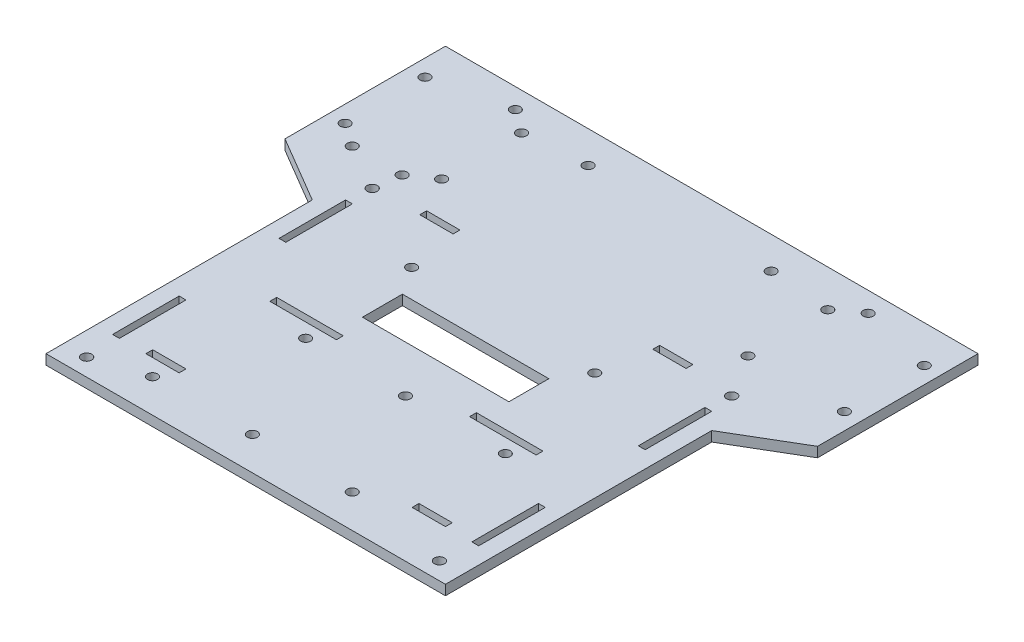
SolidWorks part; units mm, degrees
ref_plane "Front Plane" through (0, 0, 0) normal (0, 0, 1) x (1, 0, 0)
ref_plane "Top Plane" through (0, 0, 0) normal (0, 1, 0) x (1, 0, 0)
ref_plane "Right Plane" through (0, 0, 0) normal (1, 0, 0) x (0, 0, -1)
sketch "Sketch1" plane through (0, 0, 0) normal (0, 1, 0) x (1, 0, 0)
  line L0 (-60, 10) -> (-80, 21.7918)
  line L1 (60, -70) -> (-60, -70)
  line L2 (60, -70) -> (60, 70)
  line L3 (60, 70) -> (-60, 70)
  line L4 (-60, -70) -> (-60, 70)
  line L5 (60, -70) -> (-60, 70) construction
  line L6 (60, 70) -> (-60, -70) construction
  line L7 (-80, 21.7918) -> (-80, 70)
  line L8 (-80, 70) -> (-60, 70)
  line L9 (0, 0) -> (0, 70) construction
  line L10 (60, 10) -> (80, 21.7918)
  line L11 (80, 70) -> (60, 70)
  line L12 (80, 21.7918) -> (80, 70)
  point P0 (0, 0)
  dimension "D1" = 140
  dimension "D2" = 120
  dimension "D3" = 20
  dimension "D4" = 30.523
  dimension "D5" = 60
extrude "Boss-Extrude1" add sketch "Sketch1" along normal blind 3 contours L4 L1 L2 L3 | L8 L7 L0 L4 | L10 L12 L11 L2 region at (0, 0, 0) region at (-69.6368, 0, -42.8409) region at (69.6368, 0, -42.8409)
sketch "Sketch2" plane through (0, 3, 0) normal (0, 1, 0) x (1, 0, 0)
  line L2 (0, 0) -> (0, -70) construction
  line L3 (60, -70) -> (-60, -70) construction
  circle A0 centre (-38, -60) radius 1.5
  circle A1 centre (-25, -27) radius 1.5
  circle A2 centre (5, -27) radius 1.5
  circle A3 centre (-8, -60) radius 1.5
  circle A4 centre (35, -27) radius 1.5
  circle A5 centre (22, -60) radius 1.5
  dimension "D1" = 3
  dimension "D2" = 38
  dimension "D3" = 10
  dimension "D4" = 3
  dimension "D6" = 33
  dimension "D5" = 13
  dimension "D7" = 3
extrude "Cut-Extrude1" cut sketch "Sketch2" against normal through all
sketch "Sketch3" plane through (0, 3, 0) normal (0, 1, 0) x (1, 0, 0)
  line L0 (-0.0296, 57.8856) -> (-0.0296, -0.1144) construction
  line L1 (-30.0296, 33.8856) -> (29.9704, 33.8856) construction
  line L4 (-80, 21.7918) -> (-80, 70) construction
  line L6 (-80, 21.7918) -> (-80, 70) construction
  line L7 (80, 70) -> (-80, 70) construction
  line L8 (-60, 10) -> (-60, 70) construction
  line L9 (60, 10) -> (60, 70) construction
  circle A0 centre (-27.5296, 60.3856) radius 1.5
  circle A1 centre (-27.5296, 7.3856) radius 1.5
  circle A2 centre (27.4704, 7.3856) radius 1.5
  circle A3 centre (27.4704, 60.3856) radius 1.5
  point P16 (-80, 45.8959)
  dimension "D1" = 52.4704
  dimension "D2" = 36.1144
  dimension "D3" = 3
  dimension "D4" = 79.9704
  dimension "D5" = 26.5
extrude "Cut-Extrude3" cut sketch "Sketch3<2>" against normal through all
sketch "Sketch3<2>" plane through (0, 3, 0) normal (0, 1, 0) x (1, 0, 0) same geometry as "Sketch3"
extrude "Cut-Extrude2" cut sketch "Sketch3" against normal through all rebuild error yes
sketch "Sketch4" plane through (0, 3, 0) normal (0, 1, 0) x (1, 0, 0)
  line L0 (-60.5, 58.8639) -> (-60.5, 32.8639) construction
  line L1 (-80, 21.7918) -> (-80, 70) construction
  line L2 (80, 70) -> (-80, 70) construction
  line L3 (0, 0) -> (0, 70) construction
  circle A0 centre (-75, 34.8639) radius 1.5
  circle A1 centre (-75, 58.8639) radius 1.5
  circle A2 centre (-46, 34.8639) radius 1.5
  circle A3 centre (-46, 58.8639) radius 1.5
  circle A4 centre (46, 58.8639) radius 1.5
  circle A5 centre (46, 34.8639) radius 1.5
  circle A6 centre (75, 34.8639) radius 1.5
  circle A7 centre (75, 58.8639) radius 1.5
  dimension "D1" = 3
  dimension "D2" = 3
  dimension "D5" = 5
  dimension "D6" = 11.1361
  dimension "D7" = 5
  dimension "D3" = 24
  dimension "D4" = 14.5
extrude "Cut-Extrude4" cut sketch "Sketch4" against normal through all
sketch "Sketch5" plane through (0, 3, 0) normal (0, 1, 0) x (1, 0, 0)
  line L0 (80, 70) -> (-80, 70) construction
  line L1 (-80, 21.7918) -> (-80, 70) construction
  circle A0 centre (-68, 30) radius 1.5
  circle A1 centre (-53, 30) radius 1.5
  dimension "D1" = 3
  dimension "D2" = 3
  dimension "D3" = 40
  dimension "D4" = 40
  dimension "D6" = 12
  dimension "D5" = 15
extrude "Cut-Extrude5" cut sketch "Sketch5" against normal blind 3
sketch "Sketch6" plane through (0, 3, 0) normal (0, 1, 0) x (1, 0, 0)
  line L0 (60, -70) -> (-60, -70) construction
  line L1 (-45, -52.95) -> (-35, -52.95)
  line L2 (-45, -52.95) -> (-45, -55)
  line L3 (-45, -55) -> (-35, -55)
  line L4 (-35, -52.95) -> (-35, -55)
  line L5 (-45, -52.95) -> (-35, -55) construction
  line L6 (-45, -55) -> (-35, -52.95) construction
  line L7 (-60, -70) -> (-60, 10) construction
  line L8 (0, 0) -> (0, -70) construction
  line L9 (35, -52.95) -> (35, -55)
  line L10 (45, -55) -> (35, -55)
  line L11 (45, -52.95) -> (45, -55)
  line L12 (45, -52.95) -> (35, -52.95)
  line L13 (20, -22.75) -> (20, -20.7)
  line L14 (-20, -22.75) -> (-40, -22.75)
  line L15 (-20, -22.75) -> (-20, -20.7)
  line L16 (-20, -20.7) -> (-40, -20.7)
  line L17 (-40, -22.75) -> (-40, -20.7)
  line L18 (-20, -22.75) -> (-40, -20.7) construction
  line L19 (-20, -20.7) -> (-40, -22.75) construction
  line L20 (20, -22.75) -> (40, -22.75)
  line L21 (40, -22.75) -> (40, -20.7)
  line L22 (20, -20.7) -> (40, -20.7)
  line L23 (-60, -30) -> (60, -30) construction
  line L24 (60, -70) -> (60, 10) construction
  line L25 (-30, -21.725) -> (60, -21.725) construction
  line L26 (30, 24.35) -> (30, 22.3)
  line L27 (-40, 24.35) -> (-30, 24.35)
  line L28 (-40, 24.35) -> (-40, 22.3)
  line L29 (-40, 22.3) -> (-30, 22.3)
  line L30 (-30, 24.35) -> (-30, 22.3)
  line L31 (-40, 24.35) -> (-30, 22.3) construction
  line L32 (-40, 22.3) -> (-30, 24.35) construction
  line L33 (40, 24.35) -> (40, 22.3)
  line L34 (40, 24.35) -> (30, 24.35)
  line L35 (40, 22.3) -> (30, 22.3)
  circle A0 centre (-53, -64.8) radius 1.525
  circle A1 centre (53, -64.8) radius 1.525
  point P0 (-40, -53.975)
  point P16 (-30, -21.725)
  point P31 (-35, 23.325)
  dimension "D9" = 7
  dimension "D11" = 3.05
  dimension "D1" = 2.05
  dimension "D2" = 15
  dimension "D3" = 15
  dimension "D4" = 10
  dimension "D5" = 2.05
  dimension "D6" = 30.2
  dimension "D7" = 20
  dimension "D8" = 20
  dimension "D10" = 5.2
  dimension "D12" = 10
  dimension "D13" = 5
  dimension "D14" = 2.05
  dimension "D15" = 43
extrude "Cut-Extrude7" cut sketch "Sketch6" against normal through all
sketch "Sketch9" plane through (0, 3, 0) normal (0, 1, 0) x (1, 0, 0)
  line L0 (80, 70) -> (-80, 70) construction
  line L1 (-80, 21.7918) -> (-80, 70) construction
  line L2 (0, 0) -> (0, 70) construction
  circle A0 centre (-54, 22) radius 1.525
  circle A2 centre (54, 22) radius 1.525
  dimension "D1" = 3.05
  dimension "D2" = 48
  dimension "D3" = 26
extrude "Cut-Extrude8" cut sketch "Sketch9" against normal blind 3
sketch "Sketch10" plane through (0, 3, 0) normal (0, 1, 0) x (1, 0, 0)
  line L0 (60, -70) -> (60, 10) construction
  line L1 (22.0465, -12.9751) -> (-21.9535, -12.9751)
  line L2 (22.0465, -12.9751) -> (22.0465, -0.9751)
  line L3 (22.0465, -0.9751) -> (-21.9535, -0.9751)
  line L4 (-21.9535, -12.9751) -> (-21.9535, -0.9751)
  line L5 (22.0465, -12.9751) -> (-21.9535, -0.9751) construction
  line L6 (22.0465, -0.9751) -> (-21.9535, -12.9751) construction
  line L7 (80, 70) -> (-80, 70) construction
  point P0 (0.0465, -6.9751)
  dimension "D1" = 12
  dimension "D2" = 44
  dimension "D3" = 37.9535
  dimension "D4" = 70.9751
extrude "Cut-Extrude9" cut sketch "Sketch10" against normal blind 5
sketch "Sketch11" plane through (0, 3, 0) normal (0, 1, 0) x (1, 0, 0)
  line L0 (80, 70) -> (-80, 70) construction
  line L1 (0, 0) -> (0, 70) construction
  line L2 (-80, 21.7918) -> (-80, 70) construction
  circle A0 centre (-53, 64) radius 1.5
  circle A1 centre (53, 64) radius 1.5
  dimension "D1" = 3
  dimension "D3" = 27
  dimension "D2" = 6
extrude "Cut-Extrude10" cut sketch "Sketch11" against normal blind 5
sketch "Sketch12" plane through (0, 3, 0) normal (0, 1, 0) x (1, 0, 0)
  line L0 (80, 70) -> (-80, 70) construction
  line L1 (-55, 15) -> (-52.95, 15)
  line L2 (-55, 15) -> (-55, -5)
  line L3 (-55, -5) -> (-52.95, -5)
  line L4 (-52.95, 15) -> (-52.95, -5)
  line L5 (-55, 15) -> (-52.95, -5) construction
  line L6 (-55, -5) -> (-52.95, 15) construction
  line L7 (-52.95, -55) -> (-55, -55)
  line L8 (-52.95, -55) -> (-52.95, -35)
  line L9 (-52.95, -35) -> (-55, -35)
  line L10 (-55, -55) -> (-55, -35)
  line L11 (-52.95, -55) -> (-55, -35) construction
  line L12 (-52.95, -35) -> (-55, -55) construction
  line L13 (-60, -70) -> (-60, 10) construction
  line L14 (60, -70) -> (-60, -70) construction
  line L15 (0, 0) -> (0, -70) construction
  line L16 (52.95, -55) -> (55, -55)
  line L17 (52.95, -55) -> (52.95, -35)
  line L18 (55, -55) -> (55, -35)
  line L19 (52.95, -35) -> (55, -35)
  line L20 (52.95, 15) -> (52.95, -5)
  line L21 (55, -5) -> (52.95, -5)
  line L22 (55, 15) -> (55, -5)
  line L23 (55, 15) -> (52.95, 15)
  point P0 (-53.975, 5)
  point P5 (-53.975, -45)
  dimension "D1" = 20
  dimension "D2" = 55
  dimension "D3" = 2.05
  dimension "D4" = 5
  dimension "D5" = 2.05
  dimension "D6" = 20
  dimension "D7" = 5
  dimension "D8" = 15
extrude "Cut-Extrude11" cut sketch "Sketch12" against normal blind 10
